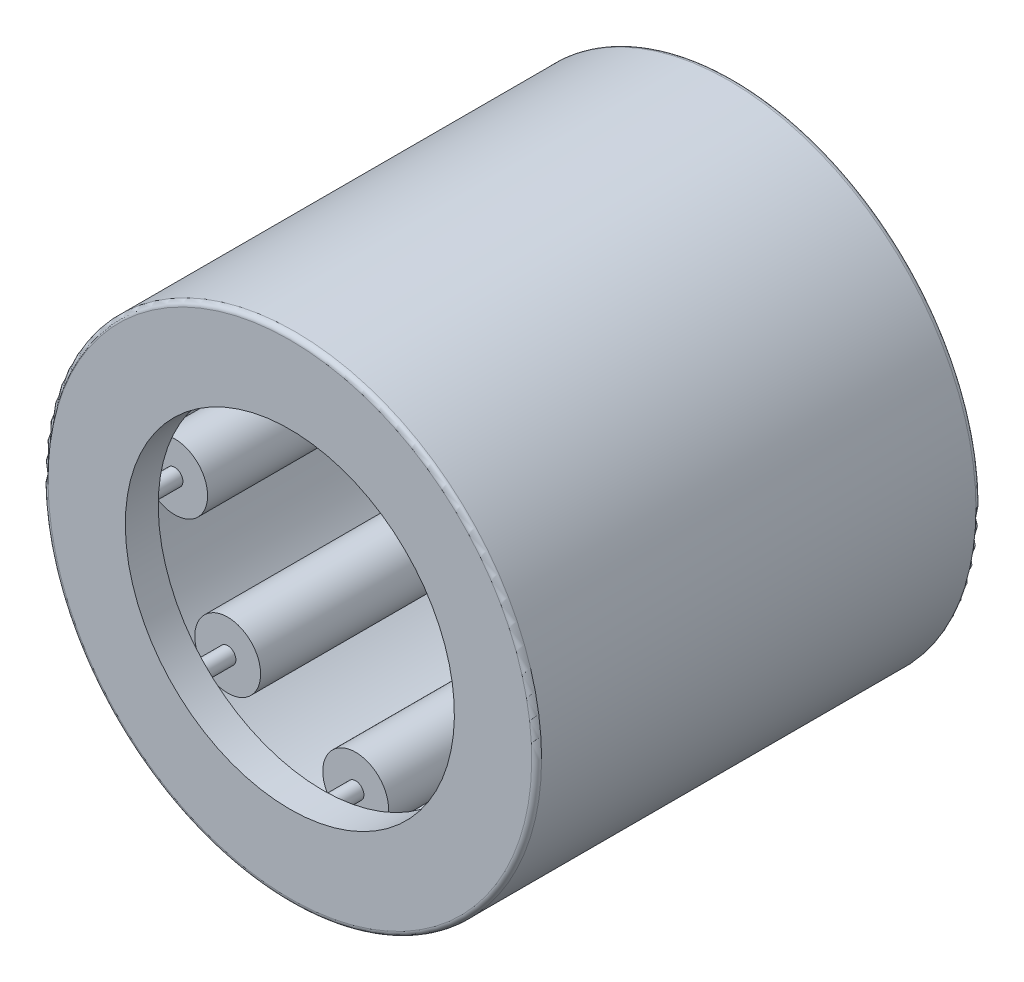
SolidWorks part; units mm, degrees
ref_plane "Front Plane" through (0, 0, 0) normal (0, 0, 1) x (1, 0, 0)
ref_plane "Top Plane" through (0, 0, 0) normal (0, 1, 0) x (1, 0, 0)
ref_plane "Right Plane" through (0, 0, 0) normal (1, 0, 0) x (0, 0, -1)
sketch "Sketch1" plane through (0, 0, 0) normal (1, 0, 0) x (0, 0, -1)
  line L0 (-4.5, 0) -> (4.5, 0) construction
  line L1 (0, 0) -> (0, 5) construction
  line L2 (-4.5, 0) -> (-4.5, 5) construction
  line L3 (-4.5, 5) -> (4.5, 5)
  line L4 (4.5, 5) -> (4.5, 0) construction
  line L5 (4.5, 0) -> (3.8333, 0) construction
  line L6 (3.8333, 0) -> (3.8333, 4.3333) construction
  line L7 (3.8333, 4.3333) -> (-3.8333, 4.3333)
  line L8 (-3.8333, 4.3333) -> (-3.8333, 0) construction
  line L9 (-3.8333, 0) -> (-4.5, 0) construction
  line L10 (-4.5, 5) -> (-4.5, 3.3333)
  line L11 (-4.5, 3.3333) -> (-3.8333, 3.3333)
  line L12 (-3.8333, 3.3333) -> (-3.8333, 4.3333)
  line L13 (3.8333, 5) -> (3.8333, 4.3333) construction
  line L14 (3.8333, 4.3333) -> (3.8333, 3.3333)
  line L15 (3.8333, 3.3333) -> (4.5, 3.3333)
  line L16 (4.5, 3.3333) -> (4.5, 5)
  line L17 (3.8333, 4.3333) -> (3.8333, 3.6667) construction
  line L18 (3.8333, 3.6667) -> (3.8333, 3) construction
  line L19 (3.8333, -4.3333) -> (3.8333, -3.6667) construction
  line L20 (3.8333, -5) -> (3.8333, -4.3333) construction
  line L21 (4.5, -3.3333) -> (4.5, -5) construction
  line L22 (3.8333, -3.3333) -> (4.5, -3.3333) construction
  line L23 (3.8333, -4.3333) -> (3.8333, -3.3333) construction
  line L24 (-3.8333, -3.3333) -> (-3.8333, -4.3333) construction
  line L25 (-4.5, -3.3333) -> (-3.8333, -3.3333) construction
  line L26 (-4.5, -5) -> (-4.5, -3.3333) construction
  line L27 (3.8333, -4.3333) -> (-3.8333, -4.3333) construction
  line L28 (-4.5, -5) -> (4.5, -5) construction
  point P4 (0, 3)
  dimension "C | Width" = 9
  dimension "Fw | ID" = 6
  dimension "D | OD" = 10
sketch "Sketch7" plane through (0, 0, 0) normal (1, 0, 0) x (0, 0, -1)
  line L0 (-4.5, 5) -> (-4.5, 3.3333) construction
  line L1 (-4.5, 3.3333) -> (-3.8333, 3.3333) construction
  line L2 (-3.8333, 3.3333) -> (-3.8333, 4.3333) construction
  line L3 (3.8333, 4.3333) -> (-3.8333, 4.3333) construction
  line L4 (3.8333, 4.3333) -> (3.8333, 3.3333) construction
  line L5 (3.8333, 3.3333) -> (4.5, 3.3333) construction
  line L6 (4.5, 3.3333) -> (4.5, 5) construction
  line L8 (-4.5, 5) -> (4.5, 5) construction
  line L9 (-4.5, 5) -> (-4.5, 3.3333)
  line L10 (-4.5, 3.3333) -> (-3.8333, 3.3333)
  line L13 (-3.8333, 3.3333) -> (-3.8333, 4.3333)
  line L16 (3.8333, 4.3333) -> (-3.8333, 4.3333)
  line L17 (3.8333, 4.3333) -> (3.8333, 3.3333)
  line L18 (3.8333, 3.3333) -> (4.5, 3.3333)
  line L19 (4.5, 3.3333) -> (4.5, 5)
  line L20 (-4.5, 5) -> (4.5, 5)
revolve "Revolve1" add sketch "Sketch7" angle 360 about L0
sketch "Sketch2" plane through (0, 0, 0) normal (1, 0, 0) x (0, 0, -1)
  line L0 (-4.5, 3.3333) -> (-3.8333, 3.3333) construction
  line L1 (-3.1667, 3.6667) -> (3.1667, 3.6667) construction
  line L2 (-3.1667, 3.6667) -> (-3.1667, 4.3333) construction
  line L3 (-3.1667, 4.3333) -> (3.1667, 4.3333)
  line L4 (3.1667, 3.6667) -> (3.1667, 4.3333) construction
  line L5 (3.8333, 3.3333) -> (4.5, 3.3333) construction
  line L6 (-3.8333, 3.6667) -> (-3.1667, 3.6667) construction
  line L7 (3.1667, 3.6667) -> (3.8333, 3.6667) construction
  line L8 (4.5, 5) -> (4.5, 0) construction
  line L9 (-3.1667, 3.8333) -> (-3.1667, 3.5) construction
  line L10 (-3.8333, 3.6667) -> (-3.8333, 3.3333) construction
  line L11 (-3.1667, 4.3333) -> (-3.1667, 3.8333)
  line L12 (3.1667, 4.3333) -> (3.1667, 3.8333)
  line L13 (3.1667, 3.8333) -> (-3.1667, 3.8333)
  line L14 (0, 4.3333) -> (0, 3) construction
  line L16 (-3.1667, 3.5) -> (-3.8333, 3.5) construction
  line L17 (0, 0) -> (4.5, 0) construction
  line L18 (-3.1667, -3.5) -> (-3.8333, -3.5) construction
  line L19 (0, -4.3333) -> (0, -3) construction
  line L20 (-3.8333, -3.6667) -> (-3.8333, -3.3333) construction
  line L21 (-3.1667, -3.8333) -> (-3.1667, -3.5) construction
  line L22 (3.1667, -3.6667) -> (3.8333, -3.6667) construction
  line L23 (-3.8333, -3.6667) -> (-3.1667, -3.6667) construction
  line L24 (3.1667, -3.6667) -> (3.1667, -4.3333) construction
  line L25 (-3.1667, -3.6667) -> (-3.1667, -4.3333) construction
  line L26 (-3.1667, -3.6667) -> (3.1667, -3.6667) construction
  line L27 (3.1667, -3.8333) -> (-3.1667, -3.8333) construction
  line L28 (3.1667, -4.3333) -> (3.1667, -3.8333) construction
  line L29 (-3.1667, -4.3333) -> (-3.1667, -3.8333) construction
  line L30 (-3.1667, -4.3333) -> (3.1667, -4.3333) construction
  line L33 (3.8333, 4.3333) -> (-3.8333, 4.3333) construction
  line L34 (3.8333, 4.3333) -> (3.8333, 3.3333) construction
  line L35 (-3.8333, 3.3333) -> (-3.8333, 4.3333) construction
  line L36 (0, 0) -> (0, 5) construction
  point P16 (0, 3.6667)
revolve "Revolve2" add sketch "Sketch2" angle 360 about L1
sketch "Sketch3" plane through (0, 0, 0) normal (1, 0, 0) x (0, 0, -1)
  line L1 (-3.8333, 3.6667) -> (3.8333, 3.6667)
  line L2 (-3.8333, 3.6667) -> (-3.8333, 3.8333)
  line L3 (-3.8333, 3.8333) -> (3.8333, 3.8333)
  line L4 (3.8333, 3.6667) -> (3.8333, 3.8333)
  line L5 (0, 0) -> (4.5, 0) construction
  line L7 (3.8333, -3.6667) -> (3.8333, -3.8333) construction
  line L8 (-3.8333, -3.8333) -> (3.8333, -3.8333) construction
  line L9 (-3.8333, -3.6667) -> (-3.8333, -3.8333) construction
  line L10 (-3.8333, -3.6667) -> (3.8333, -3.6667) construction
  line L11 (3.8333, 4.3333) -> (3.8333, 3.3333) construction
  line L12 (4.5, 5) -> (4.5, 0) construction
revolve "Revolve3" add sketch "Sketch3" angle 360 about L1
ref_axis "Axis1" through (0, 3.3333, 4.5) along (0, 1, 0)
pattern_circular "CirPattern1" count 8 every 45 about axis through (0, 0, 4.5) along (0, 0, -1) of bodies 166 167
fillet "Fillet1" radius 0.1 2 edges at (0, -5, -4.5) (0, -5, 4.5)
sketch "Front View" plane through (0, 0, 0) normal (0, 0, 1) x (1, 0, 0)
  circle A0 centre (0, 0) radius 3 construction
  circle A1 centre (0, 0) radius 5 construction
  dimension "ID" = 6
  dimension "OD" = 10
sketch "Right View" plane through (0, 0, 0) normal (1, 0, 0) x (0, 0, -1)
  line L0 (-4.5, 5) -> (4.5, 5) construction
  line L1 (-4.5, 5) -> (4.5, 5) construction
  line L2 (0, 0) -> (0, 5) construction
  point P4 (0, 5)
  dimension "Width" = 9
equation "\"Rollers@CirPattern1\"  = \"OD@Sketch1\"*.75"
equation "\"D1@Fillet1\" = \"D | OD@Sketch1\" * .01"
equation "\"Angle@CirPattern1\"=360 / \"Rollers@CirPattern1\""
equation "\"ID@Front View\" = \"Fw | ID@Sketch1\""
equation "\"OD@Front View\" = \"D | OD@Sketch1\""
equation "\"Width@Right View\" = \"C | Width@Sketch1\""
